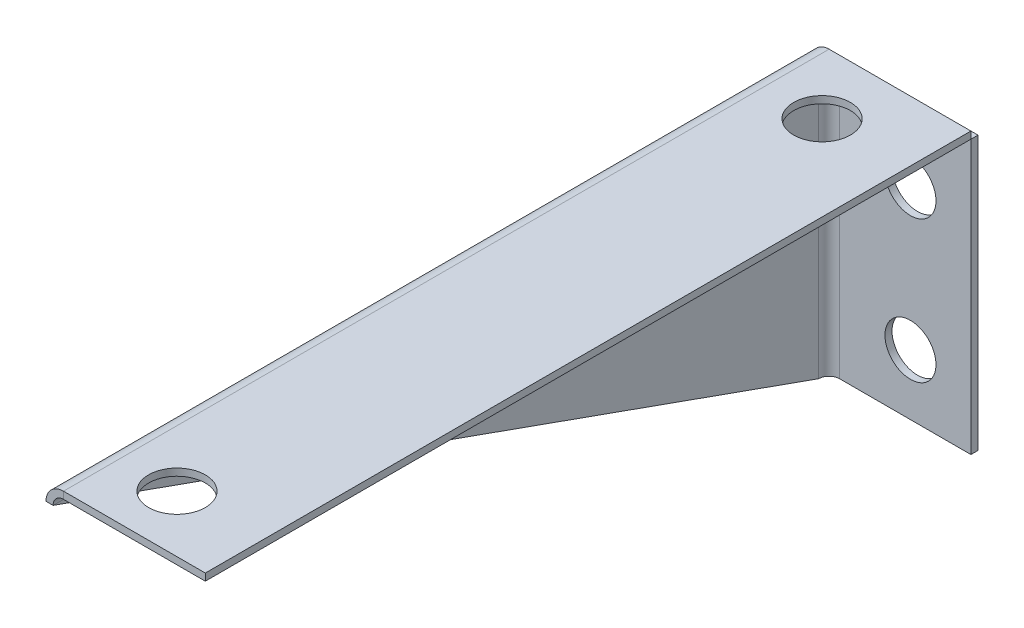
SolidWorks part; units mm, degrees
note: The reader was unsure of these and kept them because the rebuilt part matched: flange length of "Edge-Flange1", "Edge-Flange2".
ref_plane "Front Plane" through (0, 0, 0) normal (0, 0, 1) x (1, 0, 0)
ref_plane "Top Plane" through (0, 0, 0) normal (0, 1, 0) x (1, 0, 0)
ref_plane "Right Plane" through (0, 0, 0) normal (1, 0, 0) x (0, 0, -1)
sketch "Sketch1" plane through (0, 0, 0) normal (0, 1, 0) x (1, 0, 0)
  line L1 (-36.4562, 20.4635) -> (-26.4562, 20.4635)
  line L2 (-36.4562, 20.4635) -> (-36.4562, -33.5365)
  line L3 (-36.4562, -33.5365) -> (-26.4562, -33.5365)
  line L4 (-26.4562, 20.4635) -> (-26.4562, -33.5365)
  dimension "D1" = 10
  dimension "D2" = 54
sheet metal parameters "Sheet-Metal1" thickness 0.5 parameters "D1"=0.7366
base flange "Base-Flange1" sketch "Sketch1" thickness 0.5 reverse thickness direction no parameters "D1"=0.7366
edge flange "Edge-Flange1" sketch "Sketch6" flange angle 90 flange length 20 flange position bend outside bend radius 0.7366 thickness 0.5 parameters "D6"=10
sketch "Sketch6" plane through (-36.4562, -0.5, 0) normal (1, 0, 0) x (0, 0, 1)
  line L1 (33.5365, 0) -> (-20.4635, 0) construction
  line L2 (-20.4635, 0) -> (-20.4635, 20)
  line L3 (-20.4635, 20) -> (33.5365, 20)
  line L4 (33.5365, 20) -> (33.5365, 0)
  line L5 (33.5365, 0) -> (-20.4635, 0)
bend "EdgeBend1" bend radius 0.7366 bend angle 90 parameters "D5"=1
sketch "Sketch7" plane through (-37.6928, 0, 0) normal (-1, 0, 0) x (0, 0, 1)
  line L1 (-20.4635, -20.5) -> (33.5365, -1.2366)
  line L2 (33.5365, -1.2366) -> (33.5365, -20.5)
  line L3 (33.5365, -20.5) -> (-20.4635, -20.5)
extrude "Cut-Extrude1" cut sketch "Sketch7" against normal blind 10
edge flange "Edge-Flange2" sketch "Sketch10" flange angle 90 flange length 10 flange position bend outside bend radius 0.7366 thickness 0.5 parameters "D6"=10
sketch "Sketch10" plane through (-37.1928, 0, -20.4635) normal (0, 0, 1) x (0, -1, 0)
  line L1 (20.5, 0) -> (1.2366, 0) construction
  line L2 (1.2366, 0) -> (1.2366, 10)
  line L3 (1.2366, 10) -> (20.5, 10)
  line L4 (20.5, 10) -> (20.5, 0)
  line L5 (20.5, 0) -> (1.2366, 0)
bend "EdgeBend2" bend radius 0.7366 bend angle 90 parameters "D5"=2
sketch "Sketch11" plane through (0, 0, -21.7001) normal (0, 0, -1) x (-1, 0, 0)
  line L0 (27.1928, -1.2366) -> (36.4562, -1.2366) construction
  line L1 (36.4562, -20.5) -> (36.4562, -1.2366) construction
  circle A0 centre (31.4562, -6.2366) radius 1.8
  circle A1 centre (31.4562, -16.2366) radius 1.8
  dimension "D3" = 3.6
  dimension "D4" = 3.6
  dimension "D1" = 5
  dimension "D2" = 5
  dimension "D5" = 5
  dimension "D6" = 10
extrude "Cut-Extrude2" cut sketch "Sketch11" against normal blind 10
sketch "Sketch12" plane through (0, 0, 0) normal (0, 1, 0) x (1, 0, 0)
  line L0 (-36.4562, 20.4635) -> (-36.4562, -33.5365) construction
  line L1 (-36.4562, -33.5365) -> (-26.4562, -33.5365) construction
  line L2 (-26.4562, 20.4635) -> (-36.4562, 20.4635) construction
  circle A0 centre (-32.4562, -29.5365) radius 2
  circle A1 centre (-32.4562, 15.9635) radius 2
  dimension "D1" = 4
  dimension "D4" = 4
  dimension "D2" = 4
  dimension "D3" = 4
  dimension "D5" = 4.5
  dimension "D6" = 4
extrude "Cut-Extrude3" cut sketch "Sketch12" against normal blind 10
flat pattern "Flat-Pattern1" [suppressed]
sketch "Bend-Lines1" plane through (0, 0, 0) normal (0, 1, 0) x (1, 0, 0)
  line L0 (-38.0059, 21.2384) -> (-57.2693, 21.2384) construction
  line L1 (-37.231, 20.4635) -> (-37.231, -33.5365) construction
  line L2 (-38.0059, 21.2384) -> (-57.2693, 21.2384) construction
  line L3 (-37.231, 20.4635) -> (-37.231, -33.5365) construction
sketch3d "Bounding-Box1" [suppressed]
  line L0 (-57.2693, 31.2767, 0) -> (-57.2693, -33.5365, 0) construction
  line L1 (-26.4562, 31.2767, 0) -> (-26.4562, -33.5365, 0) construction
  line L2 (-57.2693, 31.2767, 0) -> (-26.4562, 31.2767, 0) construction
  line L3 (-57.2693, -33.5365, 0) -> (-26.4562, -33.5365, 0) construction
bend of the flat pattern "Flatten-<EdgeBend1>1"
bend of the flat pattern "Flatten-<EdgeBend2>1"
